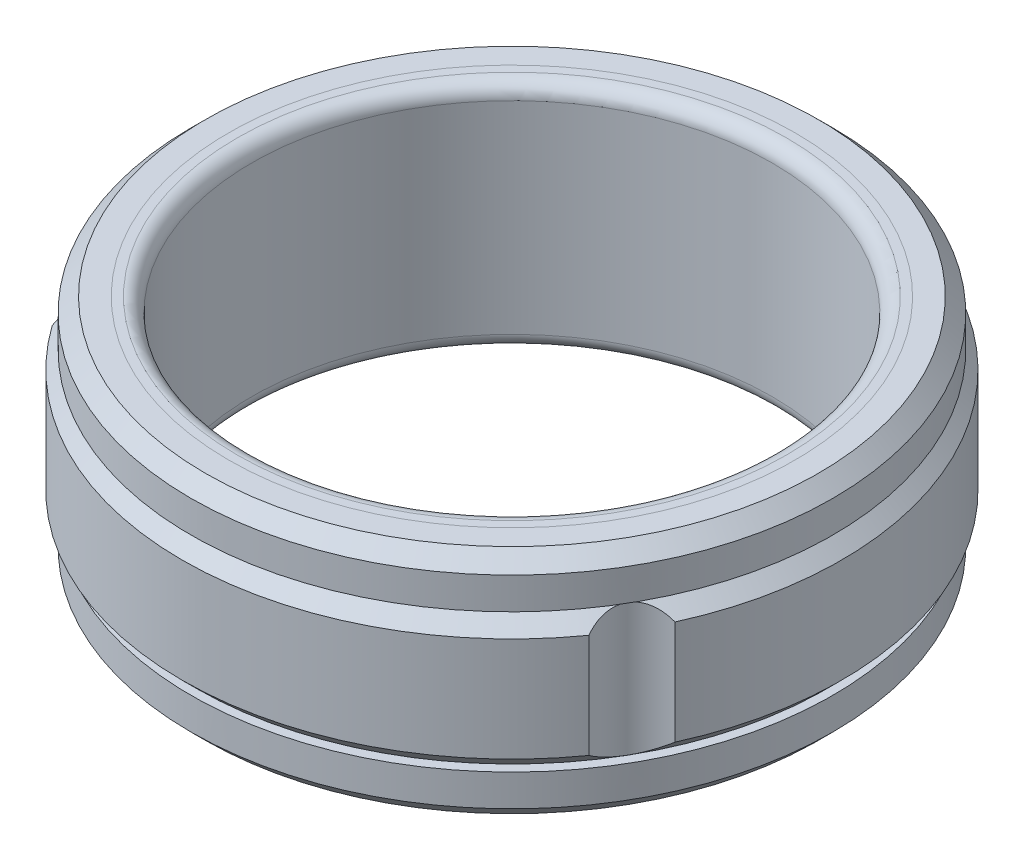
SolidWorks part; units mm, degrees
note: The reader was unsure of these and kept them because the rebuilt part matched: shared geometry of "Sketch1<3>".
ref_plane "Front Plane" through (0, 0, 0) normal (0, 0, 1) x (1, 0, 0)
ref_plane "Top Plane" through (0, 0, 0) normal (0, 1, 0) x (1, 0, 0)
ref_plane "Right Plane" through (0, 0, 0) normal (1, 0, 0) x (0, 0, -1)
sketch "Sketch1" plane through (0, 0, 0) normal (0, 0, 1) x (1, 0, 0)
  line L0 (0, 0) -> (0, 58.2704) construction
  line L2 (-9.8, 4) -> (-9, 4)
  line L3 (-9, 4) -> (-9, -4)
  line L4 (-9, -4) -> (-9.8, -4)
  line L5 (0, 0) -> (-9, 0) construction
  line L6 (-9.8, 4) -> (-9.8, 2.4)
  line L7 (-9.8, 2.4) -> (-10.3, 2.4)
  line L8 (-10.3, 2.4) -> (-10.3, -2.4)
  line L9 (-10.3, -2.4) -> (-9.8, -2.4)
  line L10 (-9.8, -2.4) -> (-9.8, -4)
  line L11 (-10.3, 2.4) -> (-11.1, 2.4)
  line L12 (-11.1, 2.4) -> (-11.1, 4)
  line L13 (-11.1, 4) -> (-9.8, 4)
  line L14 (-11.1, -4) -> (-9.8, -4)
  line L15 (-10.3, -2.4) -> (-11.1, -2.4)
  line L16 (-11.1, -2.4) -> (-11.1, -4)
  line L17 (-10.4, -2.3) -> (-10.4, 2.3)
  line L18 (-10.4, 2.3) -> (-11.4, 2.3)
  line L19 (-11.4, 2.3) -> (-11.4, -2.3)
  line L20 (-11.4, -2.3) -> (-10.4, -2.3)
  dimension "D1" = 0.8
  dimension "D2" = 1.6
  dimension "D3" = 0.5
  dimension "D4" = 18
  dimension "D5" = 4.8
  dimension "D6" = 0.8
  dimension "D7" = 0.1
  dimension "D8" = 0.1
  dimension "D9" = 1
  dimension "D10" = 8
  dimension "D11" = 2.1
revolve "Revolve1" add sketch "Sketch1" angle 360 about L0
revolve "Revolve2" add sketch "Sketch1<3>" angle 360 about L0
sketch "Sketch1<3>" plane through (0, 0, 0) normal (0, 0, 1) x (1, 0, 0) same geometry as "Sketch1"
fillet "Fillet1" radius 0.5 2 edges at (0, -4, -9) (0, 4, -9)
chamfer "Chamfer1" distance 0.5 angle 45 1 edges at (0, 4, -11.1)
chamfer "Chamfer2" distance 0.5 angle 45 1 edges at (0, -4, -11.1)
chamfer "Chamfer3" distance 0.5 angle 45 2 edges at (0, -2.3, -11.4) (0, 2.3, -11.4)
sketch "Sketch2" plane through (0, 0, 0) normal (0, 1, 0) x (1, 0, 0)
  line L0 (0, 12.5) -> (0, 0) construction
  circle A0 centre (0, 12.5) radius 1.5875
  dimension "D2" = 3.175
  dimension "D1" = 12.5
extrude "Cut-Extrude1" cut sketch "Sketch2" against normal mid plane 10
fillet "Fillet2" [suppressed] radius 0.5
pattern_circular "CirPattern1" count 3 over 360 about axis through (0, 0, 0) along (0, 1, 0) of "Cut-Extrude1"
